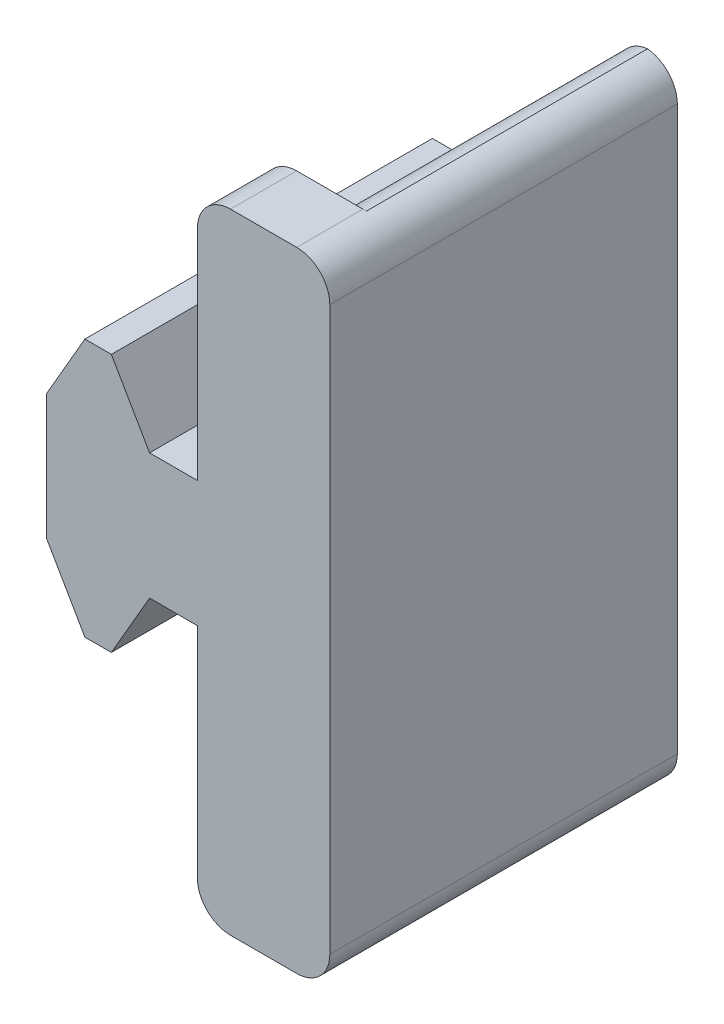
SolidWorks part; units mm, degrees
ref_plane "Alzado" through (0, 0, 0) normal (1, 0, 0) x (0, 1, 0)
ref_plane "Planta" through (0, 0, 0) normal (0, 0, 1) x (0, 1, 0)
ref_plane "Vista lateral" through (0, 0, 0) normal (0, 1, 0) x (-1, 0, 0)
sketch "Croquis1" plane through (0, 0, 0) normal (0, 0, 1) x (0, 1, 0)
  line L0 (-12.87, 0) -> (23.1864, 0) construction
  line L1 (0, 0) -> (0, 17.4542) construction
  line L2 (-3.8, 9.1094) -> (3.8, 9.1094)
  line L3 (3.8, 9.1094) -> (7.8, 6.8)
  line L4 (7.8, 6.8) -> (7.8, 5.2)
  line L5 (7.8, 5.2) -> (3.8, 2.8906)
  line L6 (3.8, 2.8906) -> (3.8, 0)
  line L7 (7.8, 6) -> (-7.8, 6) construction
  line L8 (3.8, 0) -> (19, 0)
  line L9 (19, 0) -> (19, -8)
  line L10 (19, -8) -> (-19, -8)
  line L11 (-19, 0) -> (-19, -8)
  line L12 (-3.8, 0) -> (-19, 0)
  line L13 (-3.8, 2.8906) -> (-3.8, 0)
  line L14 (-7.8, 5.2) -> (-3.8, 2.8906)
  line L15 (-7.8, 6.8) -> (-7.8, 5.2)
  line L16 (-3.8, 9.1094) -> (-7.8, 6.8)
  point P18 (0, 6)
  point P19 (0, -8)
  point P25 (0, 9.1094)
  dimension "D1" = 7.8
  dimension "D2" = 3.8
  dimension "D3" = 1.6
  dimension "D4" = 60
  dimension "D5" = 6
  dimension "D6" = 19
  dimension "D7" = 8
extrude "Saliente-Extruir1" add sketch "Croquis1" along normal blind 21
sketch "Croquis3" plane through (0, 0, 0) normal (0, 0, -1) x (1, 0, 0)
  line L0 (8, -19) -> (0, -19) construction
  line L1 (0, 19) -> (4.4, 19)
  line L2 (0, 19) -> (0, -19)
  line L3 (0, -19) -> (4.4, -19)
  line L4 (4.4, 19) -> (4.4, -19)
  dimension "D1" = 4.4
extrude "Cortar-Extruir1" cut sketch "Croquis3" against normal blind 17
fillet "Redondeo1" radius 2 6 edges at (8, 19, 10.5) (4.4, -19, 8.5) (8, -19, 10.5) (0, -19, 19) (0, 19, 19) (4.4, 19, 8.5)
chamfer "Chaflán1" distance 1 angle 45 1 edges at (0, 0, 17)
